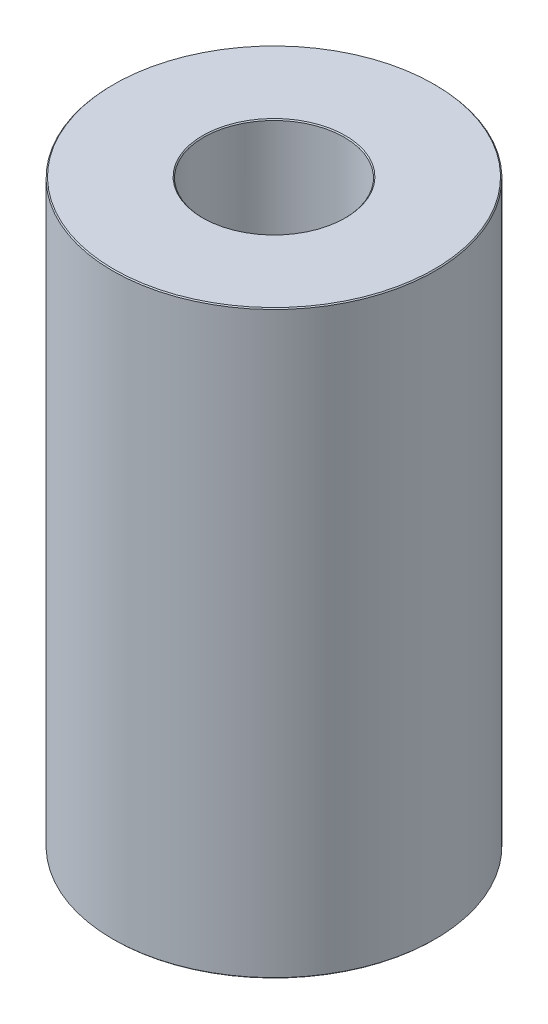
SolidWorks part; units mm, degrees
ref_plane "Front Plane" through (0, 0, 0) normal (0, 0, 1) x (1, 0, 0)
ref_plane "Top Plane" through (0, 0, 0) normal (0, 1, 0) x (1, 0, 0)
ref_plane "Right Plane" through (0, 0, 0) normal (1, 0, 0) x (0, 0, -1)
sketch "Sketch1" plane through (0, 0, 0) normal (0, 1, 0) x (1, 0, 0)
  circle A0 centre (0, 0) radius 60
  dimension "SLEEVE_OD" = 120
extrude "Boss-Extrude1" add sketch "Sketch1" along normal blind 216.1482
sketch "Sketch2" plane through (0, 0, 0) normal (0, 1, 0) x (1, 0, 0)
  circle A0 centre (0, 0) radius 26.2049
  dimension "BORE_D" = 52.4097
extrude "Cut-Extrude1" cut sketch "Sketch2" along normal through all
chamfer "Chamfer1" distance 0.3689 angle 45 4 edges at (0, 216.1482, 26.2049) (0, 0, 26.2049) (0, 0, 60) (0, 216.1482, 60)
